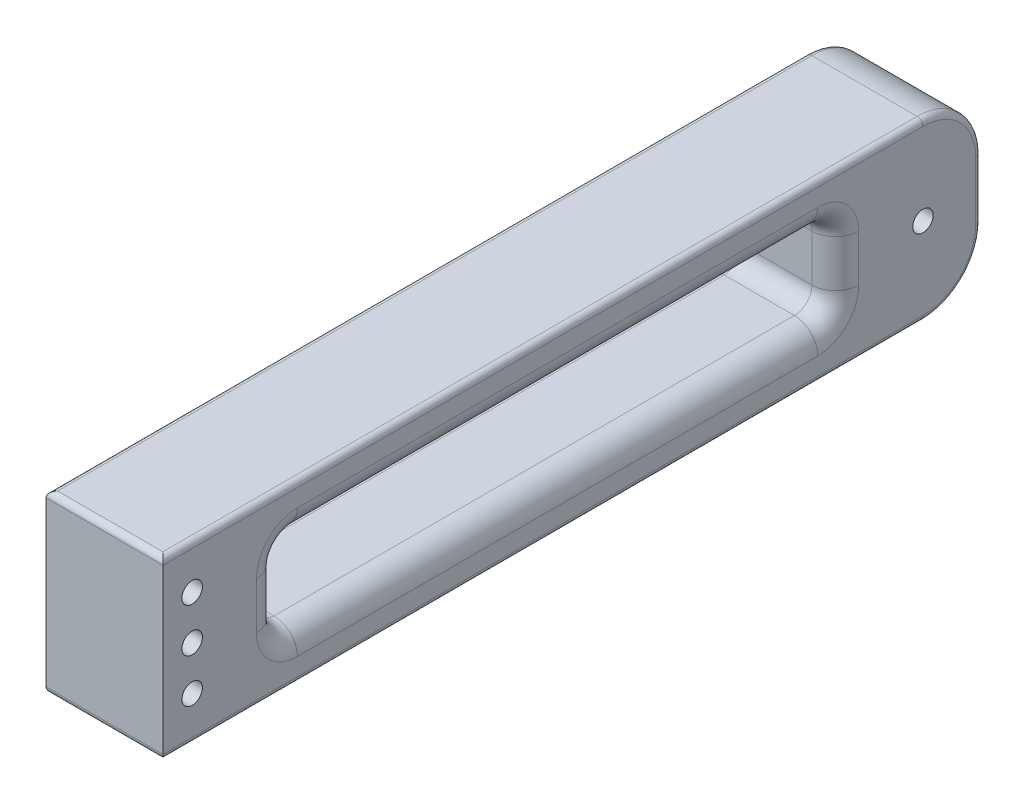
SolidWorks part; units mm, degrees
ref_plane "Front Plane" through (0, 0, 0) normal (0, 0, 1) x (1, 0, 0)
ref_plane "Top Plane" through (0, 0, 0) normal (0, 1, 0) x (1, 0, 0)
ref_plane "Right Plane" through (0, 0, 0) normal (1, 0, 0) x (0, 0, -1)
sketch "Sketch1" plane through (0, 0, 0) normal (0, 0, 1) x (1, 0, 0)
  line L1 (-10, 15) -> (10, 15)
  line L2 (-10, 15) -> (-10, -15)
  line L3 (-10, -15) -> (10, -15)
  line L4 (10, 15) -> (10, -15)
  line L5 (-10, 15) -> (10, -15) construction
  line L6 (-10, -15) -> (10, 15) construction
  point P0 (0, 0)
  dimension "D1" = 30
  dimension "D2" = 20
extrude "Boss-Extrude1" add sketch "Sketch1" along normal blind 140
fillet "Fillet1" radius 10 2 edges at (0, -15, 0) (0, 15, 0)
sketch "Sketch2" plane through (10, 0, 0) normal (1, 0, 0) x (0, 0, -1)
  line L0 (0, 0) -> (-10, 0) construction
  circle A0 centre (-10, 0) radius 1.75
  dimension "D1" = 3.5
  dimension "D2" = 10
extrude "Cut-Extrude1" cut sketch "Sketch2" against normal through all
sketch "Sketch3" plane through (-10, 0, 0) normal (-1, 0, 0) x (0, 0, 1)
  circle A2 centre (10, 0) radius 4.75
  circle A3 centre (10, 0) radius 4.75
  dimension "D1" = 3
extrude "Cut-Extrude2" cut sketch "Sketch3" against normal blind 15
sketch "Sketch4" plane through (10, 0, 0) normal (1, 0, 0) x (0, 0, -1)
  line L0 (-135, 15) -> (-135, -15) construction
  line L1 (-140, 15) -> (-10, 15) construction
  line L2 (-140, -15) -> (-10, -15) construction
  line L3 (-140, -15) -> (-140, 15) construction
  circle A0 centre (-135, 0) radius 1.75
  circle A1 centre (-135, 7.5) radius 1.75
  circle A2 centre (-135, -7.5) radius 1.75
  dimension "D1" = 3.5
  dimension "D2" = 7.5
  dimension "D3" = 7.5
  dimension "D4" = 5
extrude "Cut-Extrude3" cut sketch "Sketch4" against normal through all
fillet "Fillet2" radius 1 12 edges at (-10, -12.0711, 2.9289) (-10, 0, 0) (-10, 12.0711, 2.9289) (10, -12.0711, 2.9289) (10, 0, 0) (10, 12.0711, 2.9289) (-10, -15, 75) (10, -15, 75) (-10, 15, 75) (10, 15, 75) (0, -15, 140) (0, 15, 140)
sketch "Sketch5" plane through (10, 0, 0) normal (1, 0, 0) x (0, 0, -1)
  line L0 (-139, 15) -> (-10, 15) construction
  line L1 (-117, 7) -> (-28, 7)
  line L2 (-120, 4) -> (-120, -4)
  line L3 (-117, -7) -> (-28, -7)
  line L4 (-25, 4) -> (-25, -4)
  line L5 (-120, 7) -> (-25, -7) construction
  line L6 (-120, -7) -> (-25, 7) construction
  line L7 (-10, -15) -> (-139, -15) construction
  line L8 (-140, -14) -> (-140, 14) construction
  arc A0 (-28, 7) -> (-25, 4) centre (-28, 4) cw
  arc A1 (-28, -7) -> (-25, -4) centre (-28, -4) ccw
  arc A2 (-120, -4) -> (-117, -7) centre (-117, -4) ccw
  arc A3 (-117, 7) -> (-120, 4) centre (-117, 4) ccw
  point P0 (-72.5, 0)
  dimension "D5" = 3
  dimension "D1" = 8
  dimension "D2" = 8
  dimension "D3" = 25
  dimension "D4" = 20
extrude "Cut-Extrude4" cut sketch "Sketch5" against normal through all
fillet "Fillet3" radius 4 16 edges at (10, 6.1213, 25.8787) (10, 0, 25) (10, -6.1213, 25.8787) (10, -7, 72.5) (10, -6.1213, 119.1213) (10, 0, 120) (10, 6.1213, 119.1213) (-10, 6.1213, 25.8787) (-10, 0, 25) (-10, -6.1213, 25.8787) (-10, -7, 72.5) (-10, -6.1213, 119.1213) (-10, 0, 120) (-10, 6.1213, 119.1213) (10, 7, 72.5) (-10, 7, 72.5)
